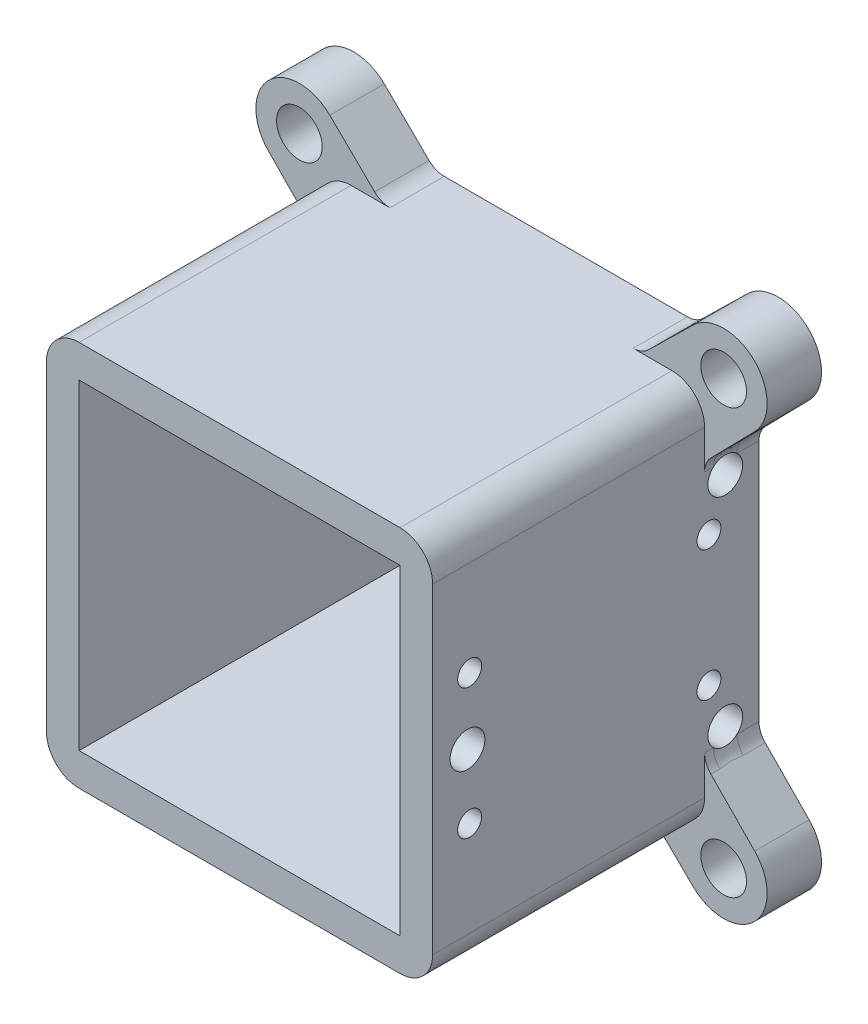
SolidWorks part; units mm, degrees
ref_plane "Front Plane" through (0, 0, 0) normal (0, 0, 1) x (1, 0, 0)
ref_plane "Top Plane" through (0, 0, 0) normal (0, 1, 0) x (1, 0, 0)
ref_plane "Right Plane" through (0, 0, 0) normal (1, 0, 0) x (0, 0, -1)
sketch "Sketch1" plane through (0, 0, 0) normal (0, 0, 1) x (1, 0, 0)
  line L0 (-17.75, 0) -> (17.75, 0) construction
  line L1 (0, 17.75) -> (0, -17.75) construction
  line L2 (-14.75, 14.75) -> (14.75, 14.75)
  line L3 (-14.75, 14.75) -> (-14.75, -14.75)
  line L4 (-14.75, -14.75) -> (14.75, -14.75)
  line L5 (14.75, 14.75) -> (14.75, -14.75)
  line L6 (-17.75, 17.75) -> (17.75, 17.75) construction
  line L7 (-17.75, 17.75) -> (-17.75, -17.75) construction
  line L8 (-17.75, -17.75) -> (17.75, -17.75) construction
  line L9 (17.75, 17.75) -> (17.75, -17.75) construction
  line L11 (-19.5, 19.5) -> (19.5, 19.5) construction
  line L12 (-17.75, 12) -> (-17.75, -12)
  line L13 (17.75, 12) -> (17.75, -12)
  line L14 (-12, 17.75) -> (12, 17.75)
  line L15 (-12, -17.75) -> (12, -17.75)
  line L16 (-17.75, 12) -> (-22.3567, 16.7001)
  line L17 (-16.7001, 22.3567) -> (-12, 17.75)
  line L18 (12, 17.75) -> (16.7001, 22.3567)
  line L19 (22.3567, 16.7001) -> (17.75, 12)
  line L20 (22.3567, -16.7001) -> (17.75, -12)
  line L21 (16.7001, -22.3567) -> (12, -17.75)
  line L22 (-22.3567, -16.7001) -> (-17.75, -12)
  line L23 (-16.7001, -22.3567) -> (-12, -17.75)
  line L24 (-19.5, 19.5) -> (-19.5, -19.5) construction
  line L25 (-19.5, -19.5) -> (19.5, -19.5) construction
  line L26 (19.5, 19.5) -> (19.5, -19.5) construction
  arc A0 (-16.7001, 22.3567) -> (-22.3567, 16.7001) centre (-19.5, 19.5) ccw
  arc A1 (22.3567, 16.7001) -> (16.7001, 22.3567) centre (19.5, 19.5) ccw
  arc A2 (16.7001, -22.3567) -> (22.3567, -16.7001) centre (19.5, -19.5) ccw
  arc A4 (-22.3567, -16.7001) -> (-16.7001, -22.3567) centre (-19.5, -19.5) ccw
  circle A5 centre (-19.5, 19.5) radius 2.1
  circle A6 centre (19.5, 19.5) radius 2.1
  circle A7 centre (19.5, -19.5) radius 2.1
  circle A8 centre (-19.5, -19.5) radius 2.1
  dimension "D6" = 8
  dimension "4.2" = 4.2
  dimension "D2" = 3
  dimension "D3" = 3
  dimension "D5" = 29.5
  dimension "D7" = 24
  dimension "D8" = 12
  dimension "D9" = 12
  dimension "D10" = 12
  dimension "D11" = 12
  dimension "D13" = 39
  dimension "D14" = 19.5
  dimension "D15" = 19.5
extrude "Boss-Extrude1" add sketch "Sketch1" along normal blind 5
sketch "Sketch2" plane through (0, 0, 5) normal (0, 0, 1) x (1, 0, 0)
  line L1 (-14.75, 14.75) -> (14.75, 14.75)
  line L2 (-14.75, 14.75) -> (-14.75, -14.75)
  line L3 (-14.75, -14.75) -> (14.75, -14.75)
  line L4 (14.75, 14.75) -> (14.75, -14.75)
  line L5 (-14.75, 17.75) -> (14.75, 17.75)
  line L6 (-17.75, 14.75) -> (-17.75, -14.75)
  line L7 (-14.75, -17.75) -> (14.75, -17.75)
  line L8 (17.75, 14.75) -> (17.75, -14.75)
  arc A0 (17.75, 14.75) -> (14.75, 17.75) centre (14.75, 14.75) ccw
  arc A1 (14.75, -17.75) -> (17.75, -14.75) centre (14.75, -14.75) ccw
  arc A2 (-14.75, -17.75) -> (-17.75, -14.75) centre (-14.75, -14.75) cw
  arc A3 (-14.75, 17.75) -> (-17.75, 14.75) centre (-14.75, 14.75) ccw
  point P12 (17.75, 17.75)
  point P15 (17.75, -17.75)
  point P20 (-17.75, 17.75)
  dimension "D5" = 3
  dimension "D1" = 3
  dimension "D2" = 3
  dimension "D3" = 3
  dimension "D4" = 3
extrude "Boss-Extrude2" add sketch "Sketch2" along normal blind 25
sketch "Sketch4" plane through (17.75, 0, 0) normal (1, 0, 0) x (0, 0, -1)
  line L0 (-26.6, 6) -> (-4.6, 6) construction
  line L1 (-26.6, -6) -> (-26.6, 6) construction
  line L2 (-4.6, 6) -> (-4.6, -6) construction
  line L3 (-26.6, -6) -> (-4.6, -6) construction
  point P0 (-26.6, 6)
  point P1 (-4.6, -6)
  point P2 (-26.6, -6)
  point P3 (-4.6, 6)
  dimension "D1" = 22
  dimension "D2" = 12
  dimension "D3" = 6
  dimension "D4" = 4.6
hole_wizard "Ø1.0mm Dowel Hole2" positions "Sketch4" profile "Sketch5" hole size "Ø1.0" standard "ISO" end condition up to next
sketch "Sketch5" plane through (17.75, 6, 26.6) normal (0, 1, 0) x (0, 0, -1)
  line L0 (0, 0) -> (0, 3)
  line L1 (0, 3) -> (1.1, 3)
  line L2 (1.1, 3) -> (1.1, 0)
  line L5 (1.1, 0) -> (0, 0)
  line L11 (0, -6.35) -> (0, 107.95) construction
  dimension "Thru Hole Dia." = 2.2
  dimension "Thru Hole Depth" = 3
sketch "Sketch6" plane through (17.75, 0, 0) normal (1, 0, 0) x (0, 0, -1)
  line L0 (0, 0) -> (-36.0191, 0) construction
  line L2 (-26.8, 10) -> (-3.1, 10) construction
  line L3 (-26.8, 10) -> (-26.8, -10) construction
  line L4 (-26.8, -10) -> (-3.1, -10) construction
  line L5 (-3.1, 10) -> (-3.1, -10) construction
  point P11 (-26.8, 0)
  point P18 (-3.1, 10)
  point P21 (-3.1, -10)
  dimension "D1" = 23.7
  dimension "D2" = 20
  dimension "D3" = 10
  dimension "D4" = 3.1
hole_wizard "Ø1.0mm Dowel Hole3" positions "Sketch6" profile "Sketch7" hole size "Ø1.0" standard "ISO" end condition up to next
sketch "Sketch7" plane through (17.75, -10, 3.1) normal (0, 1, 0) x (0, 0, -1)
  line L0 (0, 0) -> (0, 3)
  line L1 (0, 3) -> (1.6, 3)
  line L2 (1.6, 3) -> (1.6, 0)
  line L5 (1.6, 0) -> (0, 0)
  line L11 (0, -6.35) -> (0, 107.95) construction
  dimension "Thru Hole Dia." = 3.2
  dimension "Thru Hole Depth" = 3
fillet "Fillet2" radius 2 8 edges at (12, 17.75, 2.5) (-12, 17.75, 2.5) (-17.75, 12, 2.5) (-17.75, -12, 2.5) (-12, -17.75, 2.5) (12, -17.75, 2.5) (17.75, -12, 2.5) (17.75, 12, 2.5)
equation "\"D14@Sketch1\"=39/2"
equation "\"D15@Sketch1\"=39/2"
equation "\"D1@Boss-Extrude2\"=30-5mm"
equation "\"D3@Sketch4\"=12/2"
equation "\"D3@Sketch6\"=20/2"
